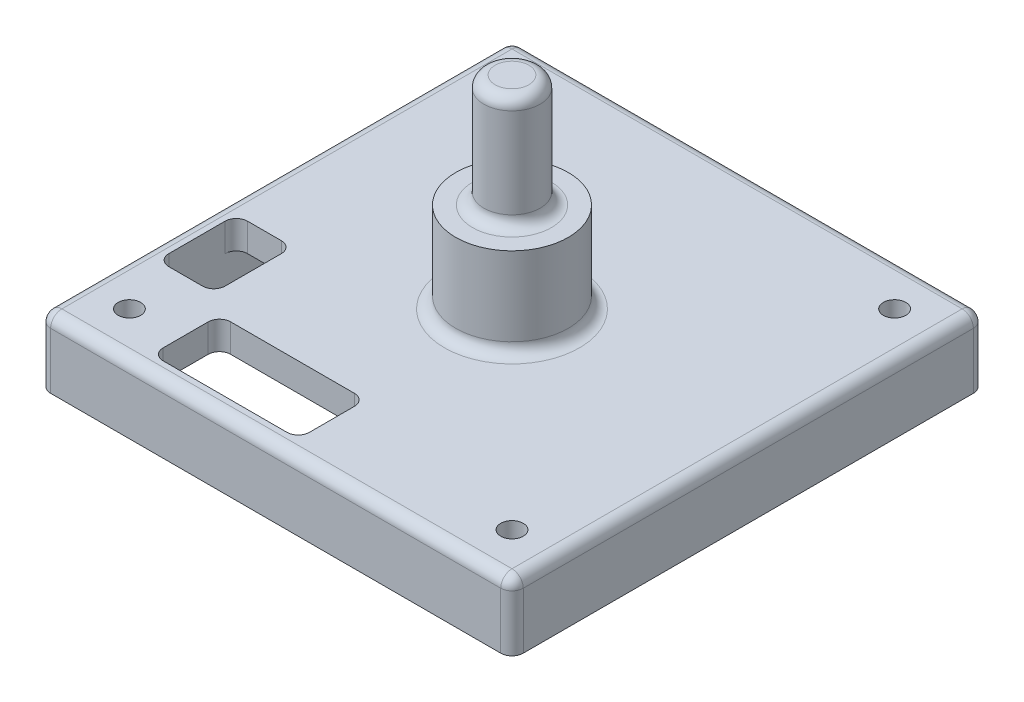
SolidWorks part; units mm, degrees
ref_plane "Front" through (0, 0, 0) normal (0, 0, 1) x (1, 0, 0)
ref_plane "Top" through (0, 0, 0) normal (0, 1, 0) x (1, 0, 0)
ref_plane "Right" through (0, 0, 0) normal (1, 0, 0) x (0, 0, -1)
sketch "Sketch1" plane through (0, 0, 0) normal (0, 1, 0) x (1, 0, 0)
  line L1 (-21, 21) -> (21, 21)
  line L2 (-21, 21) -> (-21, -21)
  line L3 (-21, -21) -> (21, -21)
  line L4 (21, 21) -> (21, -21)
  line L5 (-21, 21) -> (21, -21) construction
  line L6 (-21, -21) -> (21, 21) construction
  point P0 (0, 0)
  dimension "D1" = 42
extrude "Boss-Extrude1" add sketch "Sketch1" along normal blind 6
sketch "Sketch2" plane through (0, 0, 0) normal (0, -1, 0) x (1, 0, 0)
  line L1 (-19.5, 19.5) -> (19.5, 19.5)
  line L2 (-19.5, 19.5) -> (-19.5, -19.5)
  line L3 (-19.5, -19.5) -> (19.5, -19.5)
  line L4 (19.5, 19.5) -> (19.5, -19.5)
  line L5 (-19.5, 19.5) -> (19.5, -19.5) construction
  line L6 (-19.5, -19.5) -> (19.5, 19.5) construction
  point P0 (0, 0)
  dimension "D1" = 39
extrude "Cut-Extrude1" cut sketch "Sketch2" against normal blind 3.5
sketch "Sketch3" plane through (0, 3.5, 0) normal (0, -1, 0) x (1, 0, 0)
  line L0 (19.5, 19.5) -> (-19.5, 19.5) construction
  line L1 (-19.5, 12) -> (-14.5, 12)
  line L2 (-19.5, 12) -> (-19.5, 5)
  line L3 (-19.5, 5) -> (-14.5, 5)
  line L4 (-14.5, 12) -> (-14.5, 5)
  line L5 (-19.5, 12) -> (-14.5, 5) construction
  line L6 (-19.5, 5) -> (-14.5, 12) construction
  line L7 (-12.5, 19.5) -> (0.5, 19.5)
  line L8 (-12.5, 19.5) -> (-12.5, 13.5)
  line L9 (-12.5, 13.5) -> (0.5, 13.5)
  line L10 (0.5, 19.5) -> (0.5, 13.5)
  line L11 (-12.5, 19.5) -> (0.5, 13.5) construction
  line L12 (-12.5, 13.5) -> (0.5, 19.5) construction
  line L13 (-19.5, 19.5) -> (-19.5, -19.5) construction
  line L14 (19.5, 19.5) -> (-19.5, 19.5) construction
  point P0 (-17, 8.5)
  point P5 (-6, 16.5)
  point P16 (-7.9889, 16.75)
  dimension "D1" = 7.5
  dimension "D2" = 7
  dimension "D3" = 5
  dimension "D4" = 6
  dimension "D5" = 7
  dimension "D6" = 13
extrude "Cut-Extrude2" cut sketch "Sketch3" against normal up to next
sketch "Sketch4" plane through (0, 3.5, 0) normal (0, -1, 0) x (1, 0, 0)
  line L0 (-19.5, 17) -> (-19.5, 19.5)
  line L1 (17, -17) -> (-17, -17) construction
  line L2 (17, -17) -> (17, 17) construction
  line L3 (17, 17) -> (-17, 17) construction
  line L4 (-17, -17) -> (-17, 17) construction
  line L5 (17, -17) -> (-17, 17) construction
  line L6 (17, 17) -> (-17, -17) construction
  line L7 (-19.5, 19.5) -> (-19.5, -19.5) construction
  line L8 (-19.5, 19.5) -> (-17, 19.5)
  line L9 (-12.5, 19.5) -> (-19.5, 19.5) construction
  line L10 (0, 35.0408) -> (0, -41.1433) construction
  line L11 (-36.6087, 0) -> (46.6213, 0) construction
  line L12 (19.5, 19.5) -> (17, 19.5)
  line L13 (19.5, 17) -> (19.5, 19.5)
  line L14 (-19.5, -19.5) -> (-17, -19.5)
  line L15 (-19.5, -17) -> (-19.5, -19.5)
  line L16 (19.5, -17) -> (19.5, -19.5)
  line L17 (19.5, -19.5) -> (17, -19.5)
  arc A0 (-19.5, 17) -> (-17, 19.5) centre (-17, 17) ccw
  arc A1 (19.5, 17) -> (17, 19.5) centre (17, 17) cw
  arc A2 (-19.5, -17) -> (-17, -19.5) centre (-17, -17) cw
  arc A3 (19.5, -17) -> (17, -19.5) centre (17, -17) ccw
  point P0 (0, 0)
  dimension "D1" = 34
  dimension "D2" = 5
extrude "Boss-Extrude2" add sketch "Sketch4" along normal blind 2
sketch "Sketch5" plane through (0, 1.5, 0) normal (0, -1, 0) x (1, 0, 0)
  circle A0 centre (-17, 17) radius 1
  circle A1 centre (17, 17) radius 1
  circle A2 centre (17, -17) radius 1
  circle A3 centre (-17, -17) radius 1
  dimension "D1" = 2
extrude "Cut-Extrude3" cut sketch "Sketch5" against normal through all
sketch "Sketch6" plane through (0, 6, 0) normal (0, 1, 0) x (1, 0, 0)
  circle A0 centre (0, 0) radius 5
  dimension "D1" = 10
extrude "Boss-Extrude3" add sketch "Sketch6" along normal blind 8
sketch "Sketch7" plane through (0, 14, 0) normal (0, 1, 0) x (1, 0, 0)
  circle A0 centre (0, 0) radius 2.5
  dimension "D1" = 5
extrude "Boss-Extrude4" add sketch "Sketch7" along normal blind 10
fillet "Fillet1" radius 1 19 edges at (0, 24, 2.5) (0, 6, -21) (-21, 6, 0) (0, 6, 21) (21, 6, 0) (-21, 3, 21) (-21, 3, -21) (21, 3, -21) (21, 3, 21) (-12.5, 4.75, 13.5) (-12.5, 4.75, 19.5) (0.5, 4.75, 19.5) (0.5, 4.75, 13.5) (-19.5, 4.75, 5) (-19.5, 4.75, 12) (-14.5, 4.75, 12) (-14.5, 4.75, 5) (0, 14, 2.5) (0, 6, 5)
